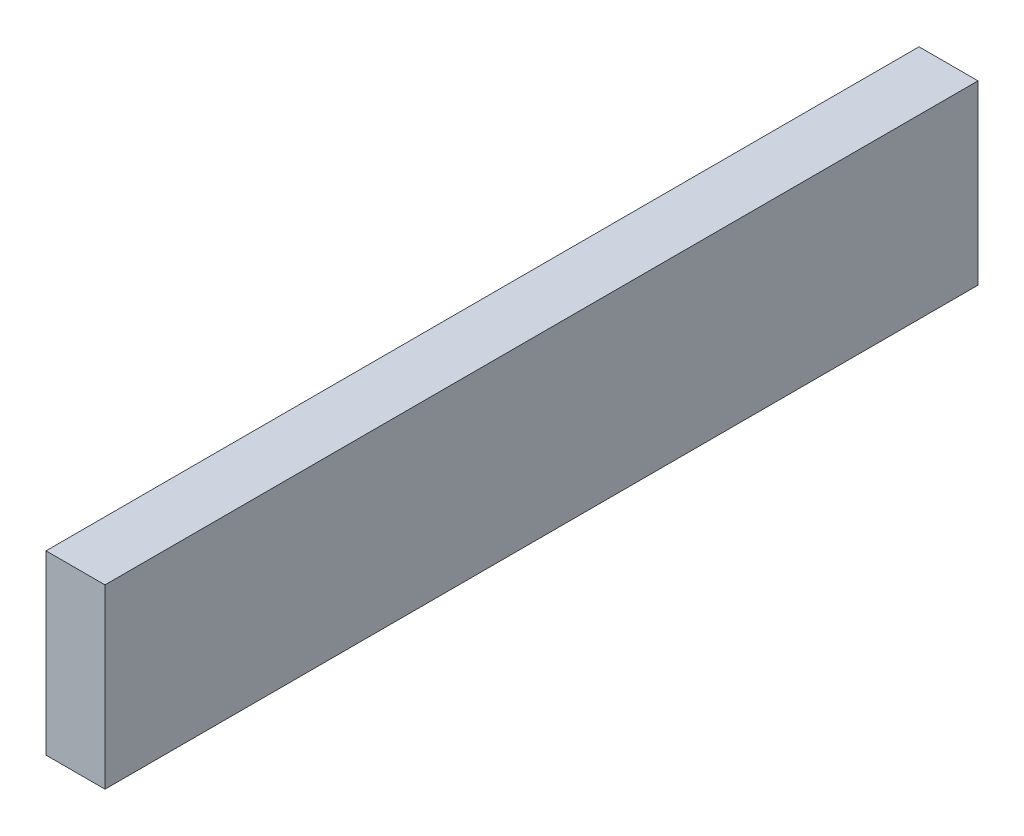
SolidWorks part; units mm, degrees
ref_plane "Front Plane" through (0, 0, 0) normal (0, 0, 1) x (1, 0, 0)
ref_plane "Top Plane" through (0, 0, 0) normal (0, 1, 0) x (1, 0, 0)
ref_plane "Right Plane" through (0, 0, 0) normal (1, 0, 0) x (0, 0, -1)
sketch "Sketch1" plane through (0, 0, 0) normal (0, 0, 1) x (1, 0, 0)
  line L1 (-7.5, 10) -> (7.5, 10)
  line L2 (-7.5, 10) -> (-7.5, -10)
  line L3 (-7.5, -10) -> (7.5, -10)
  line L4 (7.5, 10) -> (7.5, -10)
  line L5 (-7.5, 10) -> (7.5, -10) construction
  line L6 (-7.5, -10) -> (7.5, 10) construction
  point P0 (0, 0)
  dimension "D1" = 15
  dimension "D2" = 20
extrude "Boss-Extrude1" add sketch "Sketch1" along normal blind 230
sketch "Sketch2" plane through (0, 0, 0) normal (0, 0, -1) x (-1, 0, 0)
  line L1 (-32.5, 10) -> (32.5, 10)
  line L2 (-32.5, 10) -> (-32.5, 50)
  line L3 (-32.5, 50) -> (32.5, 50)
  line L4 (32.5, 10) -> (32.5, 50)
  line L6 (-7.5, 10) -> (7.5, 10) construction
  point P4 (0, 10)
  point P10 (0, 10)
  dimension "D1" = 65
  dimension "D2" = 40
extrude "Boss-Extrude6" add sketch "Sketch2" against normal blind 5 separate body
sketch "Sketch7" plane through (32.5, 0, 0) normal (1, 0, 0) x (0, 0, -1)
  line L0 (0, 50) -> (0, 10) construction
  line L1 (0, 37.5) -> (-75, 37.5)
  line L2 (0, 37.5) -> (0, 22.5)
  line L3 (0, 22.5) -> (-75, 22.5)
  line L4 (-75, 37.5) -> (-75, 22.5)
  point P4 (0, 30)
  point P7 (0, 30)
  dimension "D1" = 15
  dimension "D2" = 75
extrude "Boss-Extrude7" add sketch "Sketch7" along normal blind 5 separate body
sketch "Sketch8" plane through (-32.5, 0, 0) normal (-1, 0, 0) x (0, 0, 1)
  line L1 (0, 37.5) -> (74, 37.5)
  line L2 (0, 37.5) -> (0, 22.5)
  line L3 (0, 22.5) -> (74, 22.5)
  line L4 (74, 37.5) -> (74, 22.5)
  dimension "D1" = 74
extrude "Boss-Extrude8" add sketch "Sketch8" along normal blind 5 separate body
sketch "Sketch9" plane through (0, 0, 74) normal (0, 0, 1) x (1, 0, 0)
  line L1 (-32.5, 50) -> (32.5, 50)
  line L2 (-32.5, 50) -> (-32.5, 10)
  line L3 (-32.5, 10) -> (32.5, 10)
  line L4 (32.5, 50) -> (32.5, 10)
extrude "Boss-Extrude11" add sketch "Sketch9" against normal blind 5 separate body
sketch "Sketch10" plane through (-7.5, 0, 0) normal (-1, 0, 0) x (0, 0, 1)
  line L0 (230, 10) -> (230, -10) construction
  line L2 (209.8431, 2) -> (211.3431, 2)
  line L3 (209.8431, 2) -> (209.8431, -2)
  line L4 (209.8431, -2) -> (211.3431, -2)
  line L6 (209.8431, 2) -> (211, 0) construction
  line L7 (209.8431, -2) -> (211, 0) construction
  arc A0 (211.3431, -2) -> (211.3431, 2) centre (217, 0) ccw
  point P4 (230, 0)
  point P5 (211, 0)
  point P11 (209.8431, 0)
  dimension "D1" = 12
  dimension "D2" = 13
  dimension "D3" = 1.5
  dimension "D4" = 4
extrude "Cut-Extrude1" cut sketch "Sketch10" against normal through all
delete or keep bodies "Body-Delete/Keep 5" type delete bodies bodies 106 107 109 110
